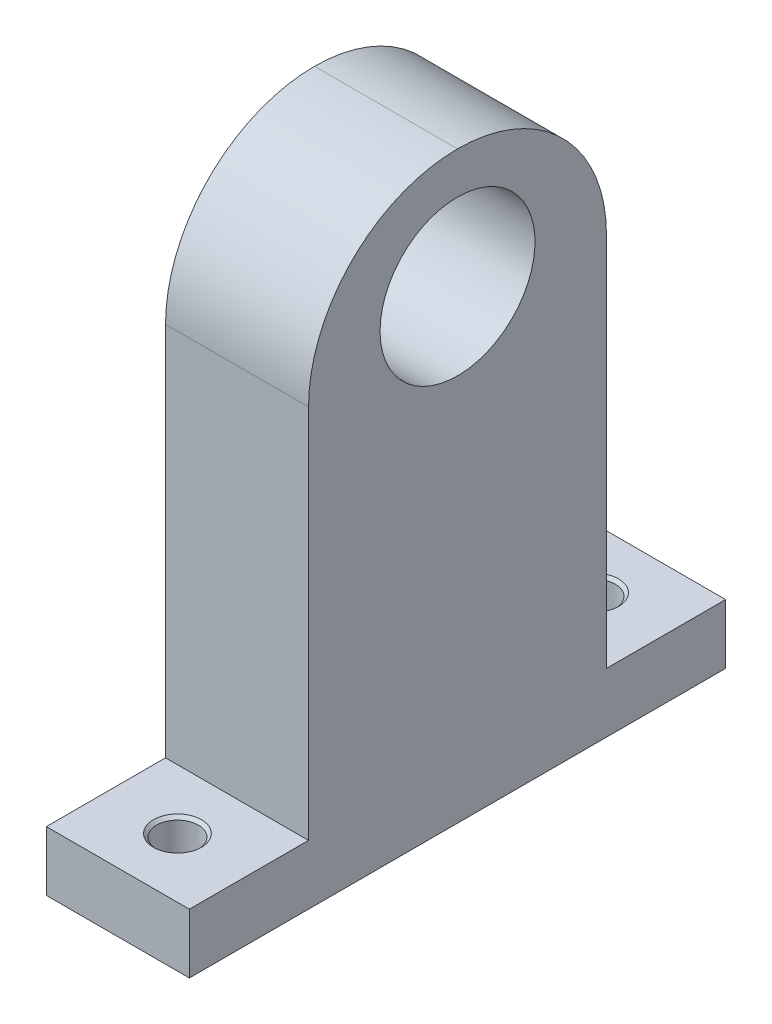
SolidWorks part; units mm, degrees
ref_plane "前视基准面" through (0, 0, 0) normal (0, 0, 1) x (1, 0, 0)
ref_plane "上视基准面" through (0, 0, 0) normal (0, 1, 0) x (1, 0, 0)
ref_plane "右视基准面" through (0, 0, 0) normal (1, 0, 0) x (0, 0, -1)
sketch "草图1" plane through (0, 0, 0) normal (0, 1, 0) x (1, 0, 0)
  line L5 (12, 37.5) -> (12, 40)
  line L6 (12, 40) -> (-12, 40)
  line L8 (-12, 37.5) -> (-12, -37.5)
  line L10 (12, 37.5) -> (12, -37.5)
  line L12 (-12, 40) -> (-12, 37.5)
  line L13 (12, -37.5) -> (12, -40)
  line L14 (-12, -37.5) -> (-12, -40)
  line L15 (-12, -40) -> (12, -40)
  point P0 (0, 0)
  dimension "D3" = 2.5
  dimension "D5" = 2.5
extrude "凸台-拉伸1" add sketch "草图1" along normal blind 10
sketch "草图2" plane through (0, 10, 0) normal (0, 1, 0) x (1, 0, 0)
  line L36 (-4, 25) -> (-12, 25)
  line L38 (-4, -25) -> (4, -25)
  line L40 (4, 25) -> (-4, 25)
  line L42 (-12, 40) -> (-12, -40) construction
  line L43 (-12, 25) -> (-12, -25)
  line L44 (-12, -25) -> (-4, -25)
  line L45 (4, 25) -> (12, 25)
  line L46 (12, -40) -> (12, 40) construction
  line L47 (12, 25) -> (12, -25)
  line L48 (12, -25) -> (4, -25)
  dimension "D1" = 50
  dimension "D2" = 8
extrude "凸台-拉伸2" add sketch "草图2" along normal blind 68
sketch "草图9" plane through (0, 78, 0) normal (0, 1, 0) x (1, 0, 0)
  line L0 (-12, 25) -> (12, 25)
  line L1 (12, 25) -> (12, -25)
  line L2 (12, -25) -> (-12, -25)
  line L3 (-12, -25) -> (-12, 25)
extrude "凸台-拉伸4" add sketch "草图9" along normal blind 20
sketch "草图10" plane through (-12, 0, 0) normal (-1, 0, 0) x (0, 0, 1)
  circle A0 centre (0, 78) radius 13
  dimension "D2" = 26
extrude "切除-拉伸3" cut sketch "草图10" against normal through all
fillet "圆角6" radius 25 2 edges at (0, 98, -25) (0, 98, 25)
sketch "草图22" plane through (0, 0, 0) normal (0, -1, 0) x (1, 0, 0)
  line L0 (-12, 40) -> (-12, 45)
  line L1 (-12, 45) -> (12, 45)
  line L2 (12, 40) -> (12, 45)
  line L3 (-12, 40) -> (12, 40)
  line L4 (-12, -40) -> (12, -40)
  line L5 (12, -40) -> (12, -45)
  line L6 (-12, -40) -> (-12, -45)
  line L7 (-12, -45) -> (12, -45)
  dimension "D1" = 5
  dimension "D2" = 5
extrude "凸台-拉伸5" add sketch "草图22" against normal blind 10
sketch "草图23" plane through (0, 10, 0) normal (0, 1, 0) x (1, 0, 0)
  line L0 (-12, 35) -> (12, 35) construction
  line L1 (-12, 45) -> (-12, 25) construction
  line L2 (12, 25) -> (12, 45) construction
  line L3 (-12, -35) -> (12, -35) construction
  line L4 (-12, -25) -> (-12, -45) construction
  line L5 (12, -45) -> (12, -25) construction
  point P14 (0, 35)
  point P16 (0, -35)
hole_wizard "M8x1.0 螺纹孔1" positions "草图23" profile "草图24" tap size "M8x1.0" standard "ANSI Metric" end condition through all
sketch "草图24" plane through (0, 10, 35) normal (1, 0, 0) x (0, 0, 1)
  line L0 (0, 0) -> (0, 10)
  line L1 (0, 10) -> (3.5, 10)
  line L2 (3.5, 10) -> (3.5, 0.525)
  line L3 (3.5, 0.525) -> (4.025, 0)
  line L5 (4.025, 0) -> (0, 0)
  line L6 (-3.5, 0.525) -> (-4.025, 0) construction
  line L11 (0, -6.35) -> (0, 107.95) construction
  dimension "通孔螺纹孔钻头直径" = 7
  dimension "通孔螺纹孔钻头深度" = 10
  dimension "近端锥形沉头孔直径" = 8.05
  dimension "近端锥形沉头孔角度" = 90
cosmetic thread "孔螺纹线1" parameters "D2"=8
cosmetic thread "孔螺纹线2" parameters "D2"=8
